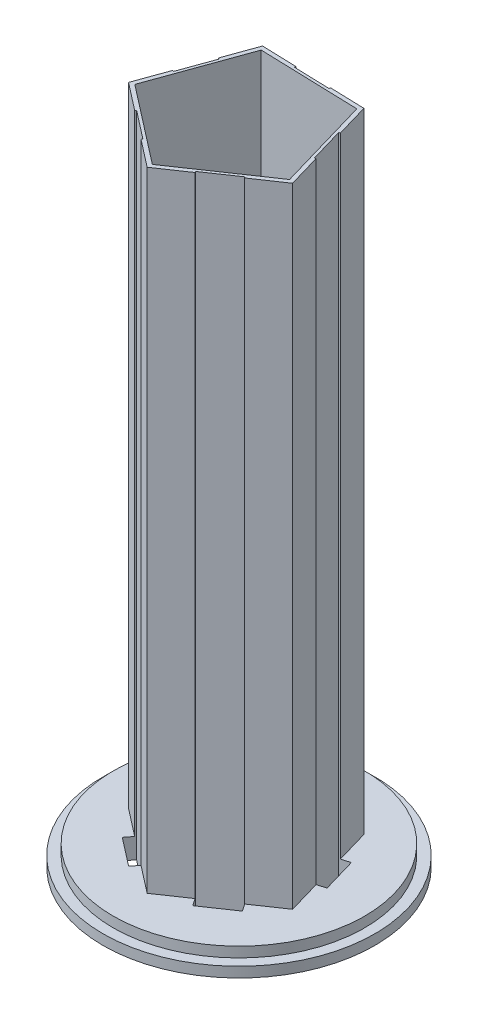
SolidWorks part; units mm, degrees
ref_plane "Front Plane" through (0, 0, 0) normal (0, 0, 1) x (1, 0, 0)
ref_plane "Top Plane" through (0, 0, 0) normal (0, 1, 0) x (1, 0, 0)
ref_plane "Right Plane" through (0, 0, 0) normal (1, 0, 0) x (0, 0, -1)
sketch "Sketch1" plane through (0, 0, 0) normal (0, 1, 0) x (1, 0, 0)
  circle A0 centre (0, 0) radius 40
  dimension "D1" = 80
extrude "Boss-Extrude1" add sketch "Sketch1" along normal blind 6
sketch "Sketch2" plane through (0, 6, 0) normal (0, 1, 0) x (1, 0, 0)
  line L0 (16.0579, 20.7082) -> (-14.7325, 21.6711)
  line L1 (23.2611, -8.3705) -> (15.1489, 19.536)
  line L2 (15.1489, 19.536) -> (-13.8986, 20.4445)
  line L3 (-13.8986, 20.4445) -> (-23.7387, -6.9006)
  line L4 (-23.7387, -6.9006) -> (-0.7728, -24.7093)
  line L5 (-0.7728, -24.7093) -> (23.2611, -8.3705)
  line L6 (-14.7325, 21.6711) -> (-25.163, -7.3147)
  line L7 (-25.163, -7.3147) -> (-0.8191, -26.1918)
  line L8 (-0.8191, -26.1918) -> (24.6568, -8.8728)
  line L9 (24.6568, -8.8728) -> (16.0579, 20.7082)
  circle A0 centre (0, 0) radius 20 construction
  dimension "D1" = 40
  dimension "D2" = 1.2
extrude "Boss-Extrude2" add sketch "Sketch2" along normal blind 185
sketch "Sketch3" plane through (0.6627, 0, -21.1896) normal (0.0313, 0, -0.9995) x (-0.9995, 0, -0.0313)
  line L0 (-15.4027, 6) -> (15.4027, 6) construction
  line L1 (-5.25, 191) -> (5.25, 191)
  line L2 (-5.25, 191) -> (-5.25, 6)
  line L3 (-5.25, 6) -> (5.25, 6)
  line L4 (5.25, 191) -> (5.25, 6)
  line L5 (-5.25, 191) -> (5.25, 6) construction
  line L6 (-5.25, 6) -> (5.25, 191) construction
  line L7 (-15.4027, 191) -> (15.4027, 191) construction
  point P0 (0, 98.5)
  point P7 (0, 6)
  point P10 (0, 0)
  dimension "D1" = 10.5
extrude "Cut-Extrude1" cut sketch "Sketch3" against normal blind 0.4
pattern_circular "CirPattern1" count 5 over 360 about axis through (0, 6, 0) along (0, -1, 0) of "Cut-Extrude1"
sketch "Sketch4" plane through (0, 6, 0) normal (0, 1, 0) x (1, 0, 0)
  line L0 (-17.7938, 11.9827) -> (-21.349, 2.1029)
  line L1 (-17.7938, 11.9827) -> (-20.6166, 12.9985)
  line L2 (-21.349, 2.1029) -> (-24.1718, 3.1187)
  line L3 (-20.6166, 12.9985) -> (-24.1718, 3.1187)
  dimension "D1" = 3
extrude "Cut-Extrude2" cut sketch "Sketch4" against normal up to surface (6 mm away) up to face at (0, 0, 40)
pattern_circular "CirPattern2" count 5 over 360 about axis through (0, 6, 0) along (0, -1, 0) of "Cut-Extrude2"
sketch "Sketch5" plane through (0, 6, 0) normal (0, 1, 0) x (1, 0, 0)
  circle A0 centre (0, 0) radius 40 construction
  circle A1 centre (0, 0) radius 40
  circle A2 centre (0, 0) radius 37
  dimension "D1" = 3
extrude "Cut-Extrude3" cut sketch "Sketch5" against normal offset from surface (3 mm away) 3 up to face at (0.6971, 0, -22.2891)
